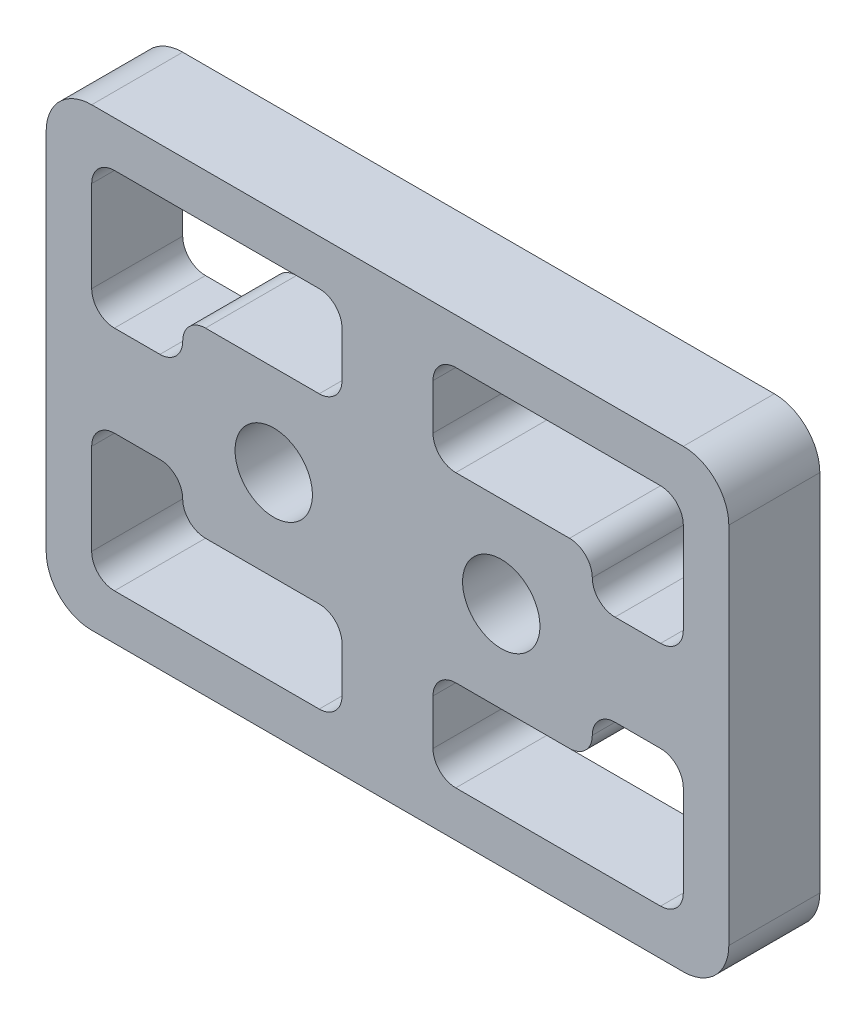
SolidWorks part; units mm, degrees
ref_plane "前视基准面" through (0, 0, 0) normal (0, 0, 1) x (1, 0, 0)
ref_plane "上视基准面" through (0, 0, 0) normal (0, 1, 0) x (1, 0, 0)
ref_plane "右视基准面" through (0, 0, 0) normal (1, 0, 0) x (0, 0, -1)
sketch "草图1" plane through (0, 0, 0) normal (0, 0, 1) x (1, 0, 0)
  line L1 (-15, -10) -> (15, -10)
  line L2 (-15, -10) -> (-15, 10)
  line L3 (-15, 10) -> (15, 10)
  line L4 (15, -10) -> (15, 10)
  line L5 (-15, -10) -> (15, 10) construction
  line L6 (-15, 10) -> (15, -10) construction
  point P0 (0, 0)
  dimension "D1" = 20
  dimension "D2" = 30
extrude "凸台-拉伸1" add sketch "草图1" along normal blind 4
fillet "圆角1" radius 2 4 edges at (-15, -10, 2) (15, -10, 2) (15, 10, 2) (-15, 10, 2)
sketch "草图2" plane through (0, 0, 4) normal (0, 0, 1) x (1, 0, 0)
  line L0 (0, 0) -> (50000, 0) construction
  line L1 (0, 0) -> (0, 50000) construction
  circle A0 centre (5, 0) radius 1.7
  circle A1 centre (-5, 0) radius 1.7
  dimension "D1" = 3.4
  dimension "D2" = 10
extrude "切除-拉伸1" cut sketch "草图2" against normal through all
sketch "草图3" plane through (0, 0, 4) normal (0, 0, 1) x (1, 0, 0)
  line L0 (-13, 2) -> (-13, 8)
  line L3 (9, 2) -> (13, 2)
  line L4 (0, 0) -> (50000, 0) construction
  line L5 (0, 0) -> (0, 50000) construction
  line L6 (-13, 8) -> (-2, 8)
  line L9 (-2, 8) -> (-2, 4)
  line L12 (9, 4) -> (9, 2)
  line L13 (-2, 4) -> (-9, 4)
  line L16 (-9, 4) -> (-9, 2)
  line L17 (-9, 2) -> (-13, 2)
  line L18 (-15, 8) -> (-15, -8) construction
  line L19 (13, 10) -> (-13, 10) construction
  line L20 (2, 4) -> (9, 4)
  line L21 (2, 8) -> (2, 4)
  line L22 (13, 8) -> (2, 8)
  line L23 (13, 2) -> (13, 8)
  line L24 (13, -2) -> (13, -8)
  line L25 (13, -8) -> (2, -8)
  line L26 (2, -8) -> (2, -4)
  line L27 (2, -4) -> (9, -4)
  line L28 (-9, -2) -> (-13, -2)
  line L29 (-9, -4) -> (-9, -2)
  line L30 (-2, -4) -> (-9, -4)
  line L31 (9, -4) -> (9, -2)
  line L32 (-2, -8) -> (-2, -4)
  line L33 (-13, -8) -> (-2, -8)
  line L34 (9, -2) -> (13, -2)
  line L35 (-13, -2) -> (-13, -8)
  dimension "D3" = 4
  dimension "D1" = 2
  dimension "D2" = 2
  dimension "D5" = 2
  dimension "D6" = 2
extrude "切除-拉伸2" cut sketch "草图3" against normal through all
fillet "圆角2" radius 1 24 edges at (-2, -4, 2) (2, 8, 2) (13, 8, 2) (13, 2, 2) (2, 4, 2) (9, 2, 2) (9, 4, 2) (13, -2, 2) (2, -8, 2) (2, -4, 2) (9, -2, 2) (9, -4, 2) (13, -8, 2) (-2, -8, 2) (-13, -8, 2) (-13, -2, 2) (-9, -2, 2) (-9, -4, 2) (-2, 8, 2) (-2, 4, 2) (-9, 4, 2) (-9, 2, 2) (-13, 2, 2) (-13, 8, 2)
equation "\"4。3\"=4.3483"
